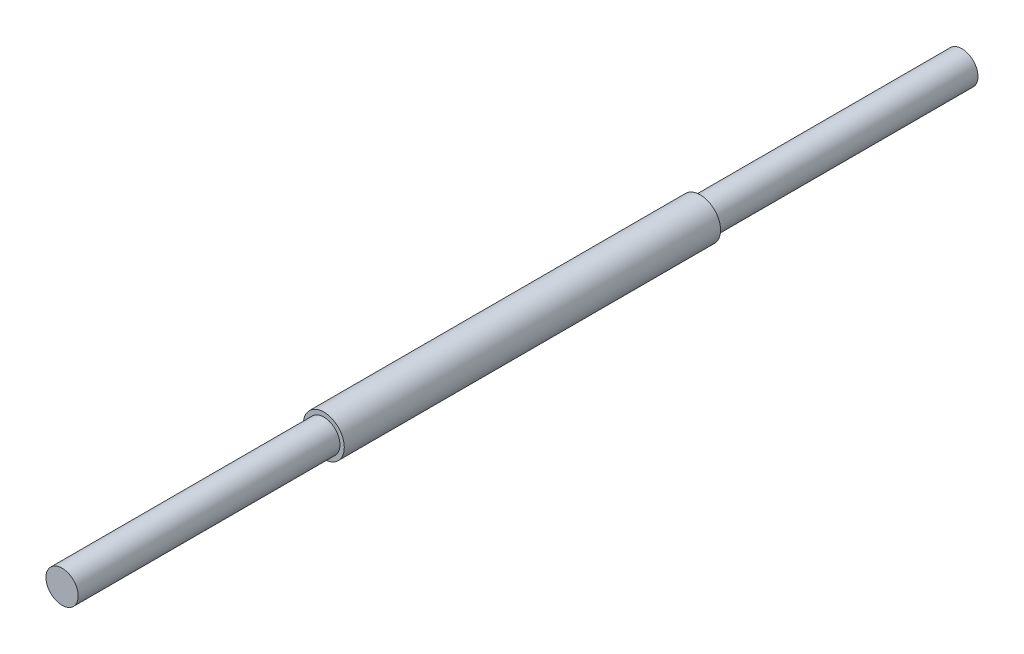
SolidWorks part; units mm, degrees
ref_plane "Front Plane" through (0, 0, 0) normal (0, 0, 1) x (1, 0, 0)
ref_plane "Top Plane" through (0, 0, 0) normal (0, 1, 0) x (1, 0, 0)
ref_plane "Right Plane" through (0, 0, 0) normal (1, 0, 0) x (0, 0, -1)
sketch "Sketch2" plane through (0, 0, 0) normal (0, 0, 1) x (1, 0, 0)
  circle A0 centre (0, 0) radius 2.5
  dimension "D1" = 5
extrude "Boss-Extrude1" add sketch "Sketch2" along normal blind 69.85 and the other way blind 69.85
sketch "Sketch3" plane through (0, 0, 0) normal (0, 0, 1) x (1, 0, 0)
  circle A0 centre (0, 0) radius 3.175
  dimension "D1" = 6.35
extrude "Boss-Extrude2" add sketch "Sketch3" along normal blind 29.21 and the other way blind 29.21
